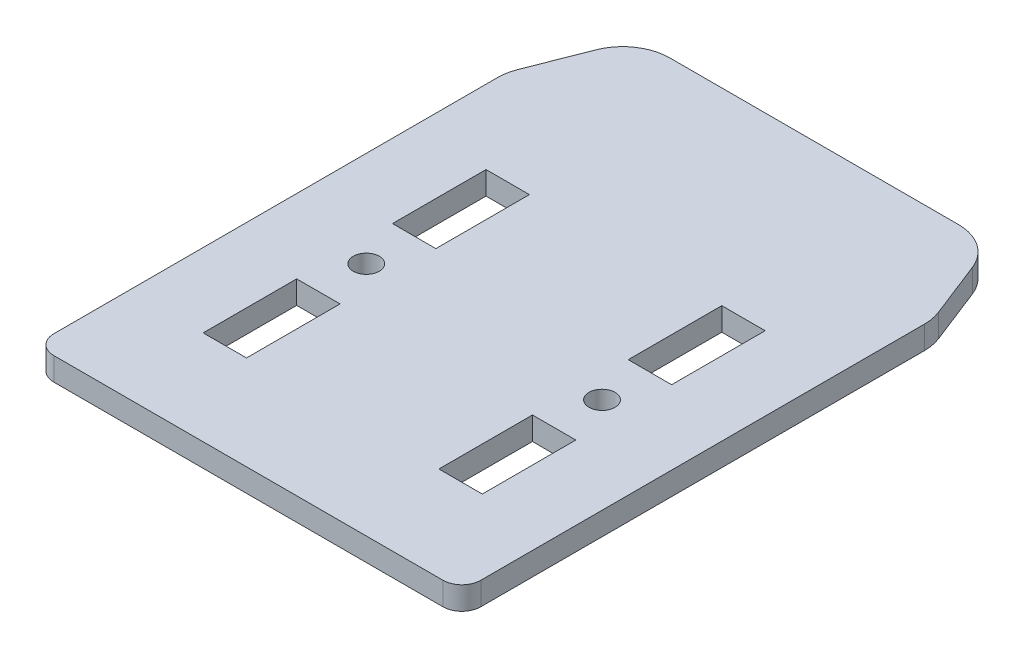
SolidWorks part; units mm, degrees
ref_plane "Front Plane" through (0, 0, 0) normal (0, 0, 1) x (1, 0, 0)
ref_plane "Top Plane" through (0, 0, 0) normal (0, 1, 0) x (1, 0, 0)
ref_plane "Right Plane" through (0, 0, 0) normal (1, 0, 0) x (0, 0, -1)
sketch "Sketch1" plane through (0, 0, 0) normal (0, 1, 0) x (1, 0, 0)
  line L0 (12.954, 0) -> (-12.954, 0) construction
  line L1 (12.954, -50.8) -> (-12.954, -50.8)
  line L2 (12.954, -25.4) -> (12.954, -12.8)
  line L3 (12.954, 50.8) -> (-12.954, 50.8)
  line L5 (12.954, -50.8) -> (-12.954, 50.8) construction
  line L6 (12.954, 50.8) -> (-12.954, -50.8) construction
  line L7 (0, -50.8) -> (0, 50.8) construction
  line L8 (-12.954, -6.35) -> (12.954, -6.35) construction
  line L9 (18.796, -12.8) -> (12.954, -12.8)
  line L10 (18.796, -12.8) -> (18.796, -25.4)
  line L11 (18.796, 0.1) -> (12.954, 0.1)
  line L12 (-18.796, 0.1) -> (-12.954, -12.8) construction
  line L13 (18.796, -12.8) -> (12.954, 0.1) construction
  line L14 (18.796, 0.1) -> (12.954, -12.8) construction
  line L15 (12.954, 0) -> (12.954, 12.7)
  line L16 (12.954, -25.4) -> (18.796, -25.4)
  line L17 (-18.796, -12.8) -> (-12.954, 0.1) construction
  line L18 (12.954, -50.8) -> (16.0528, -50.8)
  line L19 (-12.954, 0) -> (-12.954, 0.1)
  line L20 (12.954, 12.7) -> (18.796, 12.7)
  line L21 (-28.7528, 50.8) -> (-28.7528, -50.8)
  line L22 (12.954, 50.8) -> (16.0528, 50.8)
  line L23 (-16.0528, -50.8) -> (-28.7528, -50.8)
  line L24 (16.0528, 50.8) -> (28.7528, 50.8)
  line L25 (18.796, 12.7) -> (18.796, 0.1)
  line L26 (16.0528, -50.8) -> (28.7528, -50.8)
  line L27 (28.7528, 50.8) -> (28.7528, -50.8)
  line L28 (12.954, 0) -> (12.954, 0.1)
  line L29 (-18.796, 12.7) -> (-18.796, 0.1)
  line L30 (-16.0528, 50.8) -> (-28.7528, 50.8)
  line L31 (-12.954, 50.8) -> (-16.0528, 50.8)
  line L32 (-12.954, 12.7) -> (-18.796, 12.7)
  line L33 (-12.954, -50.8) -> (-16.0528, -50.8)
  line L34 (-12.954, -25.4) -> (-18.796, -25.4)
  line L35 (-12.954, 0) -> (-12.954, 0.1)
  line L36 (-18.796, 0.1) -> (-12.954, 0.1)
  line L37 (-18.796, -12.8) -> (-18.796, -25.4)
  line L38 (-18.796, -12.8) -> (-12.954, -12.8)
  line L39 (-12.954, 0) -> (-12.954, 12.7)
  line L40 (-12.954, 0) -> (-12.954, 0.1)
  line L41 (-12.954, -12.8) -> (-12.954, -25.4)
  point P0 (0, 0)
  point P10 (15.875, -6.35)
  point P37 (-15.875, -6.35)
  dimension "D1" = 25.908
  dimension "D2" = 101.6
  dimension "D3" = 5.842
  dimension "D4" = 44.45
  dimension "D5" = 12.9
  dimension "D6" = 19.05
  dimension "D7" = 19.05
  dimension "D8" = 12.7
  dimension "D9" = 15.875
extrude "Boss-Extrude1" add sketch "Sketch1" along normal blind 3.0988 contours L38 L41 L1 L18 L26 L27 L24 L22 L3 L31 L30 L21 L23 L33 L34 L37 L39 L36 L29 L32 L16 L2 L9 L10 L20 L25 L11 L15 region at (0, 0, -0.337)
sketch "Sketch2" plane through (0, 3.0988, 0) normal (0, 1, 0) x (1, 0, 0)
  line L0 (-15.875, 0.1) -> (-15.875, -12.8) construction
  line L1 (-18.796, 0.1) -> (-12.954, 0.1) construction
  line L2 (-18.796, -12.8) -> (-12.954, -12.8) construction
  line L3 (15.875, -12.8) -> (15.875, 0.1) construction
  line L4 (18.796, -12.8) -> (12.954, -12.8) construction
  line L5 (18.796, 0.1) -> (12.954, 0.1) construction
  line L6 (-18.796, -50.8) -> (-28.7528, -38.1)
  line L7 (28.7528, -50.8) -> (-28.7528, -50.8) construction
  line L8 (-28.7528, 50.8) -> (-28.7528, -50.8) construction
  line L9 (0, 50.8) -> (0, -50.8) construction
  line L10 (15.875, 0.1) -> (15.875, -12.8) construction
  line L11 (28.7528, -50.8) -> (18.796, -50.8)
  line L12 (-28.7528, 25.4) -> (-18.796, 50.8)
  line L13 (-28.7528, 50.8) -> (28.7528, 50.8) construction
  line L14 (28.7528, -38.1) -> (28.7528, -50.8)
  line L15 (-28.7528, 25.4) -> (-28.7528, 50.8)
  line L16 (-28.7528, 50.8) -> (-18.796, 50.8)
  line L17 (-28.7528, -38.1) -> (-28.7528, -50.8)
  line L18 (-28.7528, -50.8) -> (-18.796, -50.8)
  line L19 (28.7528, 50.8) -> (18.796, 50.8)
  line L20 (28.7528, 25.4) -> (28.7528, 50.8)
  line L21 (28.7528, 25.4) -> (18.796, 50.8)
  line L22 (18.796, -50.8) -> (28.7528, -38.1)
  circle A0 centre (-15.875, -6.35) radius 1.7526
  circle A1 centre (15.875, -6.35) radius 1.7526
  circle A2 centre (15.875, -6.35) radius 1.7526
  line M12 (-28.7528, -50.8) -> (28.7528, -50.8)
  line M13 (28.7528, -50.8) -> (28.7528, 50.8)
  line M14 (28.7528, 50.8) -> (-28.7528, 50.8)
  line M15 (-28.7528, 50.8) -> (-28.7528, -50.8)
  dimension "D1" = 3.5052
  dimension "D2" = 3.5052
extrude "Cut-Extrude1" cut sketch "Sketch2" against normal through all contours A0 | A1 | L21 M13 M14 | L22 M12 M13 | L6 M12 M15 | L12 M15 M14 region at (-25.4339, 3.0988, 46.5667) region at (25.4339, 3.0988, 46.5667) region at (-25.4339, 3.0988, -42.3333) region at (25.4339, 3.0988, -42.3333) region at (-15.875, 3.0988, 6.35) region at (15.875, 3.0988, 6.35)
fillet "Fillet1" radius 6.35 8 edges at (18.796, 1.5494, 50.8) (-18.796, 1.5494, 50.8) (-28.7528, 1.5494, 38.1) (-28.7528, 1.5494, -25.4) (-18.796, 1.5494, -50.8) (18.796, 1.5494, -50.8) (28.7528, 1.5494, -25.4) (28.7528, 1.5494, 38.1)
sketch "Sketch3" plane through (0, 0, 0) normal (0, -1, 0) x (-1, 0, 0)
  line L0 (-28.7528, 24.1999) -> (-28.7528, -35.9075) construction
  line L1 (-28.7528, -38.1) -> (30.0824, -38.1)
  line L2 (-28.7528, -38.1) -> (-28.7528, -50.8)
  line L3 (-28.7528, -50.8) -> (30.0824, -50.8)
  line L4 (30.0824, -38.1) -> (30.0824, -50.8)
  line L5 (-15.7055, -50.8) -> (15.7055, -50.8) construction
  dimension "D1" = 12.7
extrude "Cut-Extrude2" cut sketch "Sketch3" against normal through all
fillet "Fillet2" radius 2.54 2 edges at (-28.3623, 1.5494, 38.1) (28.3623, 1.5494, 38.1)
sketch "Sketch4" plane through (0, 0, 0) normal (0, -1, 0) x (-1, 0, 0)
  line L0 (14.4647, 50.8) -> (-14.4647, 50.8) construction
  line L1 (-35.2772, 38.1) -> (41.6124, 38.1)
  line L2 (-35.2772, 38.1) -> (-35.2772, 50.8)
  line L3 (-35.2772, 50.8) -> (41.6124, 50.8)
  line L4 (41.6124, 38.1) -> (41.6124, 50.8)
  dimension "D1" = 12.7
extrude "Cut-Extrude3" cut sketch "Sketch4" against normal through all
fillet "Fillet3" radius 6.35 2 edges at (23.7744, 1.5494, -38.1) (-23.7744, 1.5494, -38.1)
